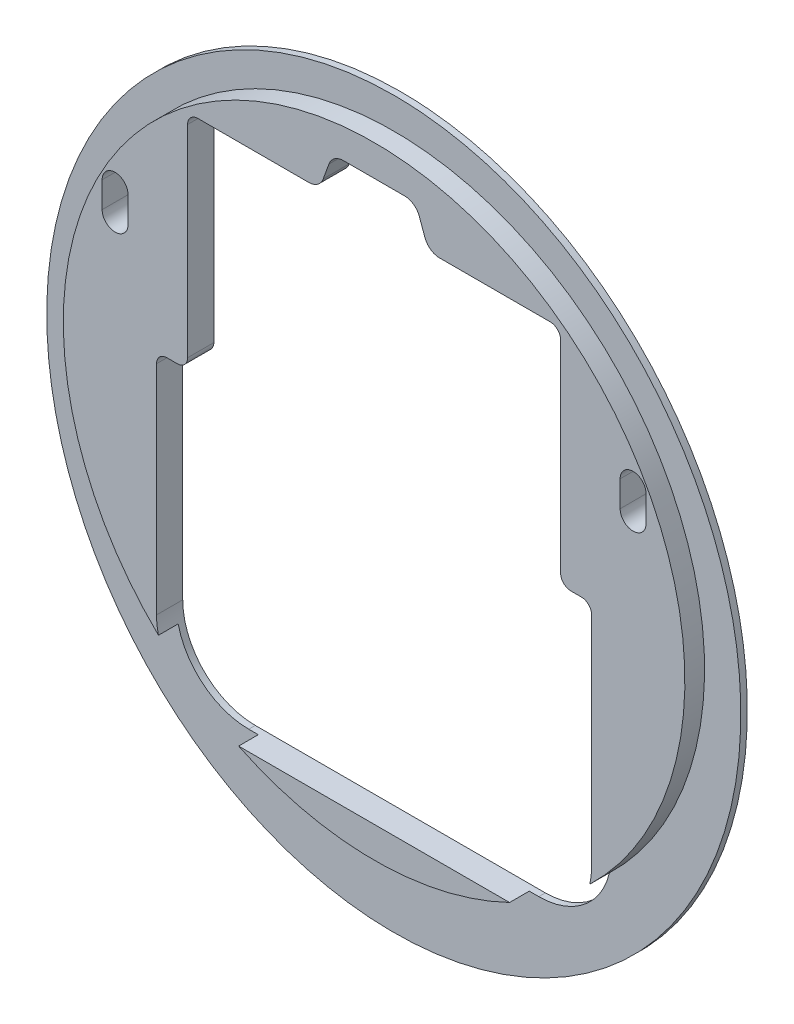
SolidWorks part; units mm, degrees
material "PA Type 6"
ref_plane "Front Plane" through (0, 0, 0) normal (0, 0, 1) x (1, 0, 0)
ref_plane "Top Plane" through (0, 0, 0) normal (0, 1, 0) x (1, 0, 0)
ref_plane "Right Plane" through (0, 0, 0) normal (1, 0, 0) x (0, 0, -1)
sketch "Sketch1" plane through (0, 0, 0) normal (0, 0, 1) x (1, 0, 0)
  line L0 (-25, 13.2531) -> (-25, 15.7531) construction
  line L3 (-26.25, 15.7531) -> (-26.25, 13.2531)
  line L9 (-23.75, 15.7531) -> (-23.75, 13.2531)
  line L12 (26.25, 15.7531) -> (26.25, 13.2531)
  line L13 (23.75, 15.7531) -> (23.75, 13.2531)
  line L65 (0, 0) -> (0, 57.9921) construction
  line L66 (2.9494, 29) -> (-2.9494, 29)
  line L67 (-4.359, 28.0126) -> (-4.9137, 26.4874)
  line L68 (-18, 24.5) -> (-18, 5)
  line L71 (-21, 3) -> (-21, -18)
  line L72 (-14, -25) -> (14, -25)
  line L75 (-6.3234, 25.5) -> (-17, 25.5)
  line L76 (-20, 4) -> (-19, 4)
  line L77 (20, 4) -> (19, 4)
  line L79 (21, 3) -> (21, -18)
  line L80 (18, 24.5) -> (18, 5)
  line L81 (6.3234, 25.5) -> (17, 25.5)
  line L82 (4.359, 28.0126) -> (4.9137, 26.4874)
  arc A16 (-21, -18) -> (-14, -25) centre (-14, -18) ccw
  arc A17 (21, -18) -> (14, -25) centre (14, -18) cw
  arc A18 (-13.0767, -25) -> (13.0767, -25) centre (0, 2) ccw
  arc A19 (20.8134, -19.6056) -> (-20.8134, -19.6056) centre (0, 2) ccw
  arc A20 (20, 4) -> (21, 3) centre (20, 3) cw
  arc A21 (-20, 4) -> (-21, 3) centre (-20, 3) ccw
  arc A22 (19, 4) -> (18, 5) centre (19, 5) cw
  arc A23 (-18, 5) -> (-19, 4) centre (-19, 5) cw
  arc A24 (18, 24.5) -> (17, 25.5) centre (17, 24.5) ccw
  arc A25 (-17, 25.5) -> (-18, 24.5) centre (-17, 24.5) ccw
  arc A26 (6.3234, 25.5) -> (4.9137, 26.4874) centre (6.3234, 27) cw
  arc A27 (-6.3234, 25.5) -> (-4.9137, 26.4874) centre (-6.3234, 27) ccw
  arc A28 (4.359, 28.0126) -> (2.9494, 29) centre (2.9494, 27.5) ccw
  arc A29 (-2.9494, 29) -> (-4.359, 28.0126) centre (-2.9494, 27.5) ccw
  arc A34 (-26.25, 13.2531) -> (-23.75, 13.2531) centre (-25, 13.2531) ccw
  arc A35 (-23.75, 15.7531) -> (-26.25, 15.7531) centre (-25, 15.7531) ccw
  arc A36 (26.25, 13.2531) -> (23.75, 13.2531) centre (25, 13.2531) cw
  arc A37 (23.75, 15.7531) -> (26.25, 15.7531) centre (25, 15.7531) cw
  ellipse E0 centre (0, 0) end of major axis (0, 35) minor radius 33.5
  point P108 (0, -25)
  point P113 (0, 29)
  point P121 (21, 4)
  point P124 (-21, 4)
  point P127 (18, 4)
  point P130 (-18, 4)
  point P133 (18, 25.5)
  point P136 (-18, 25.5)
  point P139 (5.2727, 25.5)
  point P142 (-5.2727, 25.5)
  point P145 (4, 29)
  point P148 (-4, 29)
  dimension "D5" = 25
  dimension "D7" = 2.5
  dimension "D16" = 67
  dimension "D12" = 70
  dimension "D2" = 13.2531
  dimension "D6" = 2.5
  dimension "D38" = 7
  dimension "D40" = 60
  dimension "D41" = 1
  dimension "D42" = 1.5
  dimension "D8" = 2.5
  dimension "D30" = 6
  dimension "D31" = 250.017
  dimension "D32" = 4
  dimension "D33" = 3.5
  dimension "D34" = 25
  dimension "D35" = 14
  dimension "D36" = 3
  dimension "D37" = 54
  dimension "D39" = 3
ref_plane "Plane1" through (0, 0, -10) normal (0, 0, 1) x (1, 0, 0)
ref_axis "Axis1" through (36.85, 0, -10) along (-1, 0, 0)
ref_plane "Plane2" through (0, 1.5451, -9.7553) normal (0, -0.1564, 0.9877) x (-1, 0, 0)
ref_plane "Plane3" through (0, 1.9409, -12.2541) normal (0, -0.1564, 0.9877) x (-1, 0, 0)
extrude "Boss-Extrude1" add sketch "Sketch1" along normal blind 2.53 contours L72 A18 | A29 L66 A28 L82 A26 L81 A24 L80 A22 L77 A20 L79 A17 A19 A16 L71 A21 L76 A23 L68 A25 L75 A27 L67 region at (0, 29.7914, 0) region at (0, -26.2053, 0)
extrude "Boss-Extrude3" add sketch "Sketch1<5>" along normal blind 0.63 contours A19 A17 L72 A18 A16 E0 region at (0, -34.031, 0)
sketch "Sketch1<5>" plane through (0, 0, 0) normal (0, 0, 1) x (1, 0, 0) same geometry as "Sketch1"
